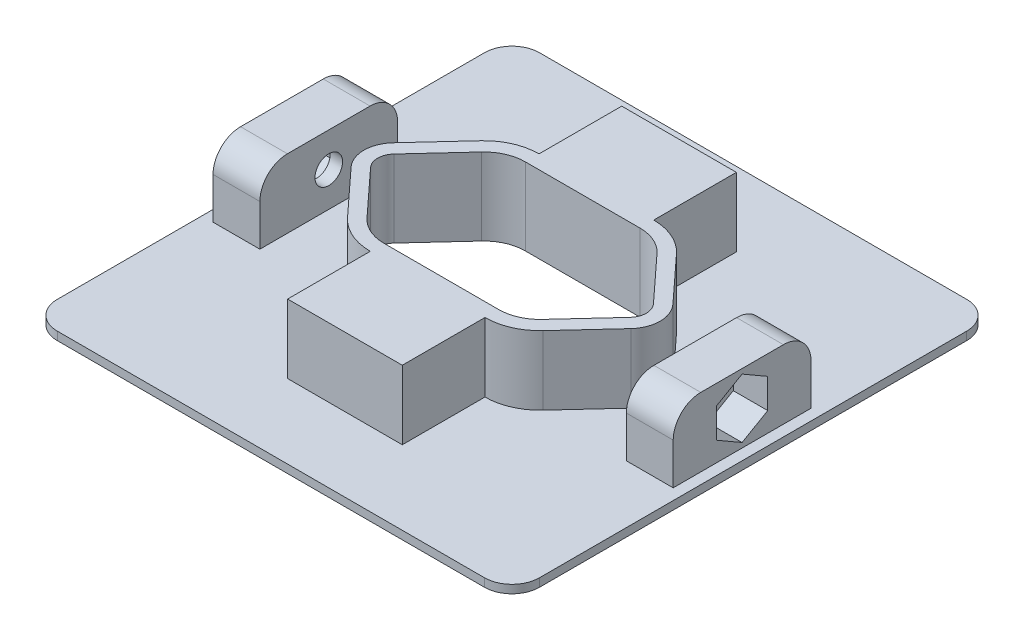
SolidWorks part; units mm, degrees
ref_plane "Front Plane" through (0, 0, 0) normal (0, 0, 1) x (1, 0, 0)
ref_plane "Top Plane" through (0, 0, 0) normal (0, 1, 0) x (1, 0, 0)
ref_plane "Right Plane" through (0, 0, 0) normal (1, 0, 0) x (0, 0, -1)
sketch "Sketch1" plane through (0, 0, 0) normal (0, 1, 0) x (1, 0, 0)
  line L1 (-35, -35) -> (35, -35)
  line L2 (-35, -35) -> (-35, 35)
  line L3 (-35, 35) -> (35, 35)
  line L4 (35, -35) -> (35, 35)
  line L5 (-35, -35) -> (35, 35) construction
  line L6 (-35, 35) -> (35, -35) construction
  point P0 (0, 0)
  dimension "D1" = 70
  dimension "D2" = 70
extrude "Boss-Extrude1" add sketch "Sketch1" along normal blind 1.2
fillet "Fillet1" radius 4 4 edges at (-35, 0.6, -35) (-35, 0.6, 35) (35, 0.6, -35) (35, 0.6, 35)
sketch "Sketch3" plane through (0, 1.2, 0) normal (0, 1, 0) x (1, 0, 0)
  line L0 (-35, 0) -> (-33.4, 0)
  line L1 (-35, 31) -> (-35, -31) construction
  line L4 (-33.4, -10) -> (-26.6, -10)
  line L5 (-33.4, -10) -> (-33.4, 10)
  line L6 (-33.4, 10) -> (-26.6, 10)
  line L7 (-26.6, -10) -> (-26.6, 10)
  line L8 (35, 0) -> (33.4, 0)
  line L9 (35, -31) -> (35, 31) construction
  line L11 (33.4, 10) -> (26.6, 10)
  line L12 (26.6, -10) -> (26.6, 10)
  line L13 (33.4, -10) -> (26.6, -10)
  line L14 (33.4, -10) -> (33.4, 10)
  dimension "D1" = 20
  dimension "D2" = 6.8
  dimension "D3" = 6.8
  dimension "D4" = 1.6
  dimension "D5" = 1.6
extrude "Boss-Extrude3" add sketch "Sketch3" along normal blind 10 contours L4 L7 L6 L5 | L13 L14 L11 L12 region at (-30, 1.2, 0) region at (30, 1.2, 0)
fillet "Fillet2" radius 4 4 edges at (30, 11.2, -10) (30, 11.2, 10) (-30, 11.2, 10) (-30, 11.2, -10)
sketch "Sketch4" plane through (-33.4, 0, 0) normal (-1, 0, 0) x (0, 0, 1)
  line L0 (0, 11.2) -> (0, 1.2)
  line L1 (6, 11.2) -> (-6, 11.2) construction
  line L2 (10, 1.2) -> (-10, 1.2) construction
  line L4 (0, 10.5) -> (-3.7239, 8.35)
  line L5 (-3.7239, 8.35) -> (-3.7239, 4.05)
  line L6 (-3.7239, 4.05) -> (0, 1.9)
  line L7 (0, 1.9) -> (3.7239, 4.05)
  line L8 (3.7239, 4.05) -> (3.7239, 8.35)
  line L9 (3.7239, 8.35) -> (0, 10.5)
  circle A0 centre (0, 6.2) radius 4.3 construction
  circle A1 centre (0, 6.2) radius 2
extrude "Cut-Extrude1" cut sketch "Sketch4" against normal blind 5 contours L5 L6 L0 L4 | L8 L9 L0 L7 region at (-33.4, 9.3438, 1.8151) region at (-33.4, 9.35, -0.0937)
sketch "Sketch5" plane through (0, 1.2, 0) normal (0, 1, 0) x (1, 0, 0)
  line L0 (18.8382, 1.6944) -> (12.7344, 8.3165)
  line L1 (8.3226, 10.25) -> (-8.3226, 10.25)
  line L2 (-12.7344, 8.3165) -> (-18.8382, 1.6944)
  line L3 (-12.7344, -8.3165) -> (-18.8382, -1.6944)
  line L4 (8.3226, -10.25) -> (-8.3226, -10.25)
  line L5 (18.8382, -1.6944) -> (12.7344, -8.3165)
  line L6 (20.3088, 3.0499) -> (14.205, 9.672)
  line L7 (8.3226, 12.25) -> (-8.3226, 12.25)
  line L8 (-14.205, 9.672) -> (-20.3088, 3.0499)
  line L9 (-14.205, -9.672) -> (-20.3088, -3.0499)
  line L10 (8.3226, -12.25) -> (-8.3226, -12.25)
  line L11 (20.3088, -3.0499) -> (14.205, -9.672)
  arc A0 (12.7344, 8.3165) -> (8.3226, 10.25) centre (8.3226, 4.25) ccw
  arc A1 (-8.3226, 10.25) -> (-12.7344, 8.3165) centre (-8.3226, 4.25) ccw
  arc A2 (-18.8382, 1.6944) -> (-18.8382, -1.6944) centre (-17, 0) ccw
  arc A3 (-8.3226, -10.25) -> (-12.7344, -8.3165) centre (-8.3226, -4.25) cw
  arc A4 (12.7344, -8.3165) -> (8.3226, -10.25) centre (8.3226, -4.25) cw
  arc A5 (18.8382, 1.6944) -> (18.8382, -1.6944) centre (17, 0) cw
  arc A6 (14.205, 9.672) -> (8.3226, 12.25) centre (8.3226, 4.25) ccw
  arc A7 (-8.3226, 12.25) -> (-14.205, 9.672) centre (-8.3226, 4.25) ccw
  arc A8 (-20.3088, 3.0499) -> (-20.3088, -3.0499) centre (-17, 0) ccw
  arc A9 (-8.3226, -12.25) -> (-14.205, -9.672) centre (-8.3226, -4.25) cw
  arc A10 (14.205, -9.672) -> (8.3226, -12.25) centre (8.3226, -4.25) cw
  arc A11 (20.3088, 3.0499) -> (20.3088, -3.0499) centre (17, 0) cw
extrude "Cut-Extrude2" cut sketch "Sketch5" against normal through all contours L1 A1 L2 A2 L3 A3 L4 A4 L5 A5 L0 A0
extrude "Boss-Extrude4" add sketch "Sketch5<3>" along normal blind 10
sketch "Sketch5<3>" plane through (0, 1.2, 0) normal (0, 1, 0) x (1, 0, 0) same geometry as "Sketch5"
sketch "Sketch13" plane through (-33.4, 0, 0) normal (-1, 0, 0) x (0, 0, 1)
  circle A0 centre (0, 6.2) radius 2
extrude "Cut-Extrude10" cut sketch "Sketch13" against normal up to surface (6.8 mm away) up to face at (-26.6, 6.8095, 0)
sketch "Sketch14" plane through (33.4, 0, 0) normal (1, 0, 0) x (0, 0, -1)
  line L0 (0, 11.2) -> (0, 1.2)
  line L1 (0, 10.5) -> (-3.7239, 8.35)
  line L2 (-3.7239, 8.35) -> (-3.7239, 4.05)
  line L3 (-3.7239, 4.05) -> (0, 1.9)
  line L4 (0, 1.9) -> (3.7239, 4.05)
  line L5 (3.7239, 4.05) -> (3.7239, 8.35)
  line L6 (3.7239, 8.35) -> (0, 10.5)
  line L7 (-6, 11.2) -> (6, 11.2)
  line L8 (-6, 11.2) -> (6, 11.2) construction
  circle A0 centre (0, 6.2) radius 4.3 construction
  arc A1 (-6, 11.2) -> (-10, 7.2) centre (-6, 7.2) ccw construction
  circle A2 centre (0, 6.2) radius 2
extrude "Cut-Extrude11" cut sketch "Sketch14" against normal blind 5 contours A2 L0 L4 L5 L6 | A2 L0 L1 L2 L3 region at (33.4, 9.3438, -1.8151) region at (33.4, 9.35, 0.0937)
extrude "Cut-Extrude12" cut sketch "Sketch14<4>" against normal up to surface (6.8 mm away) contours L0 A2 | L0 A2 region at (33.4, 6.2, -0.8488) region at (33.4, 6.2, 0.8488) up to face at (26.6, 6.8095, 0)
sketch "Sketch14<4>" plane through (33.4, 0, 0) normal (1, 0, 0) x (0, 0, -1) same geometry as "Sketch14"
sketch "Sketch15" plane through (0, 0, 12.25) normal (0, 0, 1) x (1, 0, 0)
  line L1 (-8.3226, 11.2) -> (8.3226, 11.2)
  line L2 (-8.3226, 11.2) -> (-8.3226, 1.2)
  line L3 (-8.3226, 1.2) -> (8.3226, 1.2)
  line L4 (8.3226, 11.2) -> (8.3226, 1.2)
extrude "Boss-Extrude5" add sketch "Sketch15" along normal blind 12
sketch "Sketch16" plane through (0, 0, -12.25) normal (0, 0, -1) x (-1, 0, 0)
  line L1 (-8.3226, 11.2) -> (8.3226, 11.2)
  line L2 (-8.3226, 11.2) -> (-8.3226, 1.2)
  line L3 (-8.3226, 1.2) -> (8.3226, 1.2)
  line L4 (8.3226, 11.2) -> (8.3226, 1.2)
extrude "Boss-Extrude6" add sketch "Sketch16" along normal blind 12
